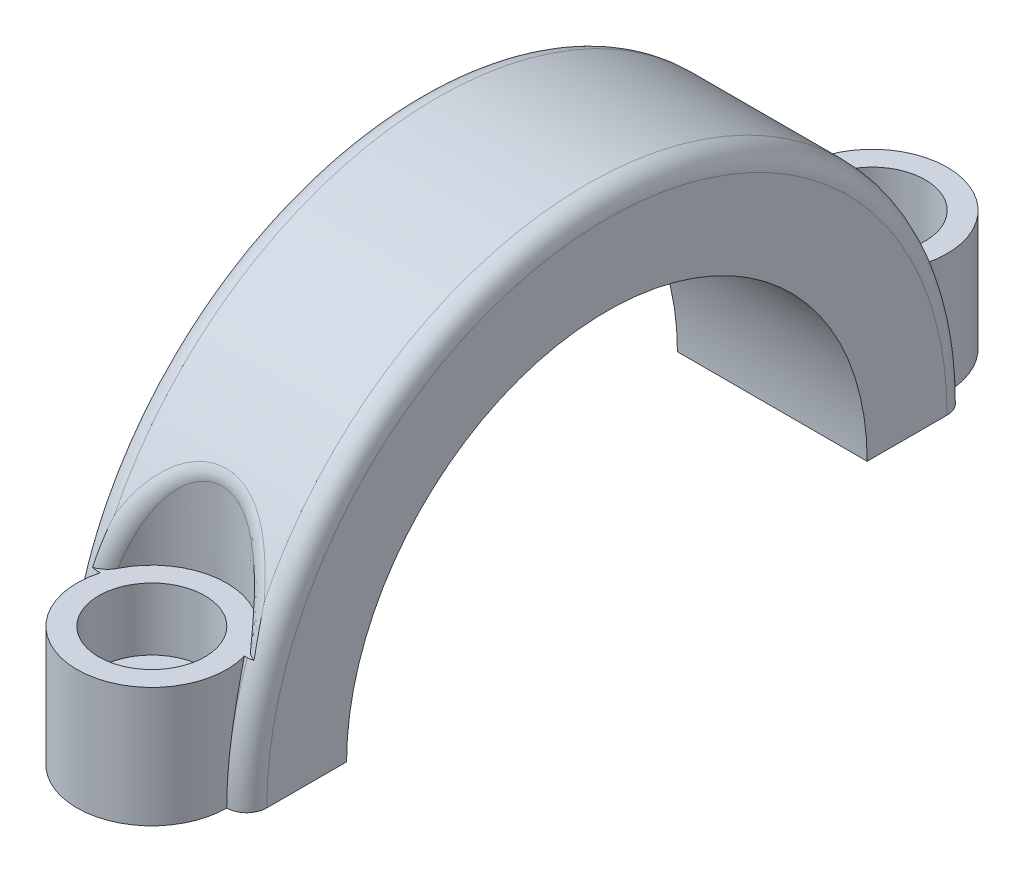
SolidWorks part; units mm, degrees
note: The reader was unsure of these and kept them because the rebuilt part matched: shared geometry of "Sketch2<3>".
ref_plane "Front Plane" through (0, 0, 0) normal (0, 0, 1) x (1, 0, 0)
ref_plane "Top Plane" through (0, 0, 0) normal (0, 1, 0) x (1, 0, 0)
ref_plane "Right Plane" through (0, 0, 0) normal (1, 0, 0) x (0, 0, -1)
sketch "Sketch1" plane through (0, 0, 0) normal (1, 0, 0) x (0, 0, -1)
  line L0 (-45.8, 0) -> (-33.1, 0)
  line L1 (33.1, 0) -> (45.8, 0)
  arc A0 (33.1, 0) -> (-33.1, 0) centre (0, 0) ccw
  arc A1 (45.8, 0) -> (-45.8, 0) centre (0, 0) ccw
  circle A2 centre (0, 0) radius 45.8 construction
  circle A3 centre (0, 0) radius 33.1 construction
  dimension "D2" = 66.2
  dimension "D1" = 12.7
extrude "Boss-Extrude1" add sketch "Sketch1" along normal mid plane 24.13
sketch "Sketch2" plane through (0, 0, 0) normal (0, -1, 0) x (1, 0, 0)
  line L0 (12.065, -45.8) -> (-12.065, -45.8) construction
  circle A0 centre (0, -45.8) radius 9.525
  dimension "D1" = 19.05
extrude "Boss-Extrude2" add sketch "Sketch2" against normal blind 15.25
extrude "Cut-Extrude4" cut sketch "Sketch2<3>" against normal blind 15.25 draft 3 from offset 15.25 offset against normal yes
sketch "Sketch2<3>" plane through (0, 0, 0) normal (0, -1, 0) x (1, 0, 0) same geometry as "Sketch2"
hole_wizard "CBORE for 5/16 Socket Head Cap Screw1" positions "3DSketch1" profile "Sketch4" counterbore size "5/16" standard "ANSI Inch"
sketch3d "3DSketch1"
  line L0 (0, 15.25, -45.8) -> (0, 27.1329, -45.8) construction
  point P0 (0, 15.25, -45.8)
  point P4 (0, 78.4035, -61.5275)
  point P8 (0, 15.25, -45.8)
sketch "Sketch4" plane through (0, 15.25, -45.8) normal (1, 0, 0) x (0, 0, 1)
  line L0 (0, 0) -> (0, 15.25)
  line L1 (0, 15.25) -> (4.2164, 15.25)
  line L3 (4.2164, 15.25) -> (4.2164, 7.9375)
  line L4 (4.2164, 7.9375) -> (6.7475, 7.9375)
  line L5 (6.7475, 7.9375) -> (6.7475, 0)
  line L7 (6.7475, 0) -> (0, 0)
  line L11 (0, -6.35) -> (0, 107.95) construction
  dimension "Thru Hole Dia." = 8.4328
  dimension "Thru Hole Depth" = 15.25
  dimension "C'Bore Dia." = 13.495
  dimension "C'Bore Depth" = 7.9375
mirror "Mirror1" about plane through (0, 0, 0) normal (0, 0, 1) of "Cut-Extrude4", "Boss-Extrude2", "CBORE for 5/16 Socket Head Cap Screw1"
fillet "Fillet1" radius 2.54 2 edges at (-0.764, 27.0912, 36.9284) (-0.764, 27.0912, -36.9284)
fillet "Fillet2" radius 2.54 2 edges at (-12.065, 45.8, 0) (12.065, 45.8, 0)
